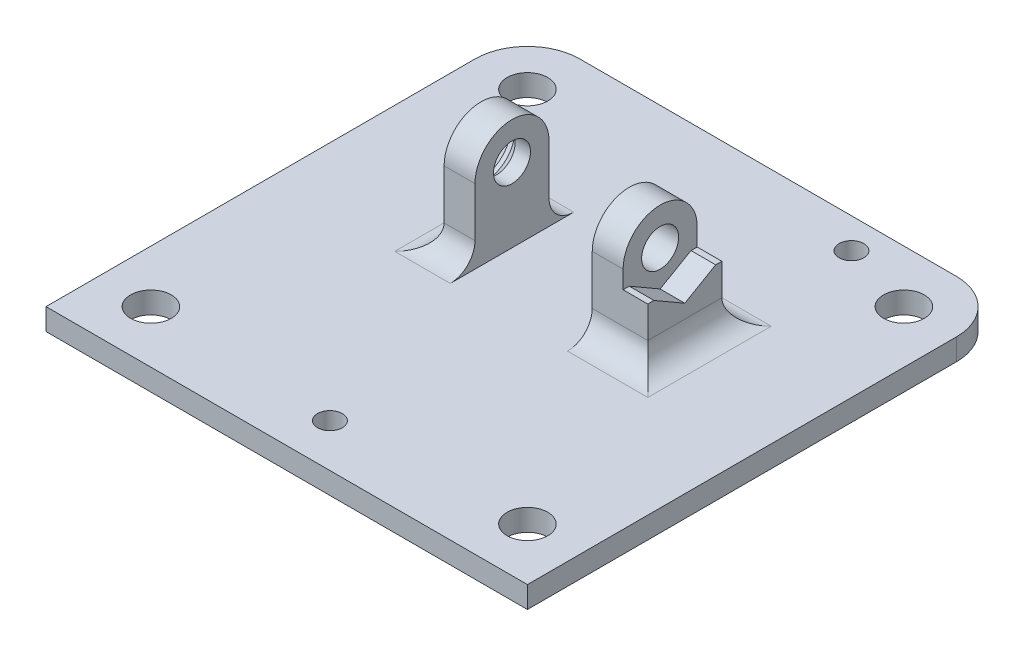
SolidWorks part; units mm, degrees
ref_plane "Front Plane" through (0, 0, 0) normal (0, 0, 1) x (1, 0, 0)
ref_plane "Top Plane" through (0, 0, 0) normal (0, 1, 0) x (1, 0, 0)
ref_plane "Right Plane" through (0, 0, 0) normal (1, 0, 0) x (0, 0, -1)
sketch "Sketch1" plane through (0, 0, 0) normal (0, 1, 0) x (1, 0, 0)
  line L0 (-19.5, 35.2) -> (-19.5, -19.5) construction
  line L1 (-19.5, 19.5) -> (19.5, 19.5)
  line L2 (-19.5, 19.5) -> (-19.5, -19.5)
  line L3 (-19.5, -19.5) -> (19.5, -19.5)
  line L4 (19.5, 19.5) -> (19.5, -19.5)
  line L5 (-19.5, 19.5) -> (19.5, -19.5) construction
  line L6 (-19.5, -19.5) -> (19.5, 19.5) construction
  line L7 (-19.5, -19.5) -> (19.5, -19.5) construction
  line L8 (0, -19.5) -> (0, 19.5) construction
  circle A0 centre (-15.25, -15.25) radius 1.65 construction
  circle A1 centre (15.25, -15.25) radius 1.65 construction
  circle A2 centre (9.2, 17.05) radius 1 construction
  circle A3 centre (15.25, 15.25) radius 1.65 construction
  circle A4 centre (-15.25, 15.25) radius 1.65 construction
  circle A5 centre (-15.25, -15.25) radius 1.65
  circle A6 centre (15.25, -15.25) radius 1.65
  circle A7 centre (9.2, 17.05) radius 1
  circle A8 centre (15.25, 15.25) radius 1.65
  circle A9 centre (-15.25, 15.25) radius 1.65
  circle A10 centre (-15.25, 15.25) radius 4.25
  circle A11 centre (15.25, 15.25) radius 4.25
  circle A12 centre (-15.25, -15.25) radius 4.25
  circle A13 centre (15.25, -15.25) radius 4.25
  circle A14 centre (0, -16) radius 1
  point P0 (0, 0)
  dimension "D1" = 2
  dimension "D2" = 3.5
extrude "Shape" add sketch "Sketch1" along normal blind 1.75 contours A13 L4 A11 L1 A10 L2 A12 L3 A7 | A10 A9 | A11 A8 | A13 A6 | A12 A5 | A12 L2 L3 | A13 L3 L4 region at (-0.0227, 0, 0.0026) region at (-12.3298, 0, -18.1702) region at (18.1702, 0, -18.1702) region at (-18.5507, 0, 18.5507) region at (-15.25, 0, 11.1202) region at (18.1702, 0, 18.1702) region at (18.5507, 0, 18.5507)
sketch "Sketch3" plane through (0, 1.75, 0) normal (0, 1, 0) x (1, 0, 0)
  line L0 (0, 19.5) -> (0, -19.5) construction
  line L1 (-15.25, 19.5) -> (15.25, 19.5) construction
  line L2 (-19.5, -19.5) -> (19.5, -19.5) construction
  line L3 (-19.5, 3.5) -> (19.5, 3.5) construction
  line L4 (-19.5, 15.25) -> (-19.5, -19.5) construction
  line L5 (19.5, 15.25) -> (19.5, -19.5) construction
  line L6 (4.75, 6.5) -> (7.25, 6.5)
  line L7 (-4.75, 6.5) -> (-7.25, 6.5)
  line L8 (-4.75, 6.5) -> (-4.75, 0.5)
  line L9 (-4.75, 0.5) -> (-7.25, 0.5)
  line L10 (-7.25, 6.5) -> (-7.25, 0.5)
  line L11 (-4.75, 6.5) -> (-7.25, 0.5) construction
  line L12 (-4.75, 0.5) -> (-7.25, 6.5) construction
  line L13 (4.75, 6.5) -> (4.75, 0.5)
  line L14 (4.75, 0.5) -> (7.25, 0.5)
  line L15 (7.25, 6.5) -> (7.25, 0.5)
  line L17 (7.25, 6.5) -> (9.25, 6.5)
  line L18 (7.25, 6.5) -> (7.25, 0.5)
  line L19 (7.25, 0.5) -> (9.25, 0.5)
  line L20 (9.25, 6.5) -> (9.25, 0.5)
  point P12 (-6, 3.5)
  dimension "D1" = 16
  dimension "D2" = 9.5
  dimension "D3" = 2.5
  dimension "D4" = 6
  dimension "D5" = 4.5
extrude "Supports" add sketch "Sketch3" along normal blind 9 contours L7 L10 L9 L8 | L15 L6 L13 L14 | L20 L17 L15 L19 region at (6, 1.75, -3.5) region at (8.25, 1.75, -3.5) region at (-6, 1.75, -3.5)
sketch "Sketch4" plane through (-7.25, 0, 0) normal (-1, 0, 0) x (0, 0, 1)
  line L0 (-3.5, 10.75) -> (-3.5, 1.75) construction
  line L2 (-6.5, 1.75) -> (-0.5, 1.75) construction
  line L3 (-0.5, 10.75) -> (-0.5, 1.75) construction
  line L4 (-6.5, 10.75) -> (-0.5, 10.75) construction
  circle A0 centre (-3.5, 7.75) radius 3
  circle A1 centre (-3.5, 7.75) radius 1.5
  point P13 (0, 0)
  line M2 (-0.5, 1.75) -> (-0.5, 10.75)
  line M4 (-6.5, 10.75) -> (-6.5, 1.75)
  line M11 (-0.5, 10.75) -> (-6.5, 10.75)
  dimension "D1" = 3
extrude "Support cuts" cut sketch "Sketch4" against normal up to surface (16.5 mm away) contours A1 L0 | L0 A1 | A0 M11 M4 | A0 M2 M11 region at (-7.25, 10.0799, -1.1701) region at (-7.25, 10.0799, -5.8299) region at (-7.25, 7.75, -2.8634) region at (-7.25, 7.75, -4.1366) up to face at (9.25, 6.25, -3.5)
fillet "Fillet1" radius 2 6 edges at (-6, 1.75, -6.5) (7, 1.75, -6.5) (7, 1.75, -0.5) (-6, 1.75, -0.5) (-7.25, 1.75, -3.5) (9.25, 1.75, -3.5)
sketch "Sketch5" plane through (9.25, 0, 0) normal (1, 0, 0) x (0, 0, -1)
  line L0 (1, 6.3066) -> (0.5, 6.3066)
  line L1 (3.5, 4.8632) -> (6, 6.3066)
  line L2 (6, 6.3066) -> (6, 9.1934)
  line L3 (6, 9.1934) -> (3.5, 10.6368)
  line L4 (3.5, 10.6368) -> (1, 9.1934)
  line L5 (1, 9.1934) -> (1, 6.3066)
  line L6 (1, 6.3066) -> (3.5, 4.8632)
  line L7 (6, 6.3066) -> (6.5, 6.3066)
  line L9 (0.5, 7.75) -> (0.5, 3.75)
  line L10 (0.5, 3.75) -> (6.5, 3.75)
  line L11 (6.5, 3.75) -> (6.5, 7.75)
  line L12 (0.5, 7.75) -> (0.5, 3.75)
  line L13 (0.5, 3.75) -> (6.5, 3.75)
  line L14 (6.5, 3.75) -> (6.5, 7.75)
  circle A0 centre (3.5, 7.75) radius 2.5 construction
  circle A1 centre (3.5, 7.75) radius 1.5 construction
  arc A2 (6.5, 7.75) -> (0.5, 7.75) centre (3.5, 7.75) ccw
  arc A3 (6.5, 7.75) -> (0.5, 7.75) centre (3.5, 7.75) ccw
  circle M3 centre (3.5, 7.75) radius 1.5
  line M4 (0.5, 7.75) -> (0.5, 3.75)
  line M6 (6.5, 3.75) -> (6.5, 7.75)
  arc M7 (6.5, 7.75) -> (0.5, 7.75) centre (3.5, 7.75) ccw
  dimension "D1" = 5
  dimension "D2" = 0
extrude "Nut holder" cut sketch "Sketch5" against normal blind 2 contours L5 L6 L1 L2 L3 L4 M3 | L2 L7 L0 L5 L4 L3 M6 M7 M4 region at (9.25, 6.3813, -0.75) region at (9.25, 7.75, -1.0764)
sketch "Sketch6" plane through (-7.25, 0, 0) normal (-1, 0, 0) x (0, 0, 1)
  circle A0 centre (-3.5, 7.75) radius 2.4
  dimension "D1" = 4.8
extrude "Screw cut" cut sketch "Sketch6" against normal blind 0.35
chamfer "Scew chamfer" distance 0.9 angle 45 1 edges at (-6.9, 7.75, -2)
